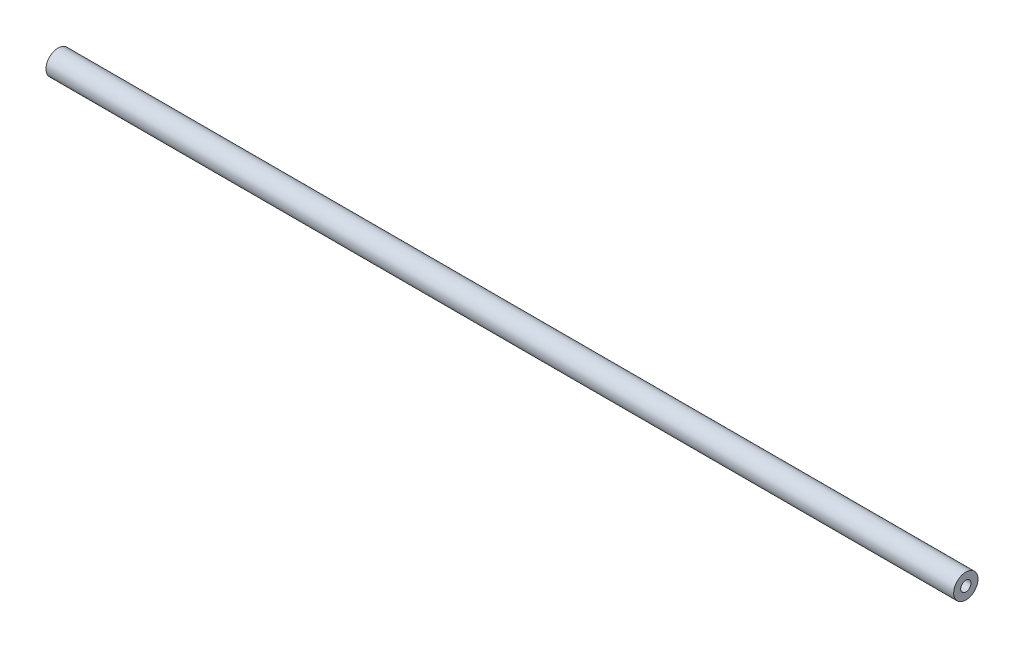
SolidWorks part; units mm, degrees
material "7075-T6 (SN)"
ref_plane "Front Plane" through (0, 0, 0) normal (0, 0, 1) x (1, 0, 0)
ref_plane "Top Plane" through (0, 0, 0) normal (0, 1, 0) x (1, 0, 0)
ref_plane "Right Plane" through (0, 0, 0) normal (1, 0, 0) x (0, 0, -1)
sketch "Sketch1" plane through (0, 0, 0) normal (1, 0, 0) x (0, 0, -1)
  circle A1 centre (0, 0) radius 4.7625
  dimension "D1" = 9.525
extrude "Boss-Extrude1" add sketch "Sketch1" along normal mid plane 355.6 contours A1 region at (0, 0, 0)
hole_wizard "#10-32 Tapped Hole1" positions "3DSketch1" profile "Sketch2" tap size "#10-32" standard "ANSI Inch"
sketch3d "3DSketch1"
  line L0 (177.8, 0, 0) -> (-177.8, 0, 0) construction
  point P0 (177.8, 0, 0)
  point P7 (-177.8, 0, 0)
sketch "Sketch2" plane through (177.8, 0, 0) normal (0, 1, 0) x (0, 0, -1)
  line L0 (0, 0) -> (0, 13.2428)
  line L1 (0, 13.2428) -> (2.0193, 12.0294)
  line L2 (2.0193, 12.0294) -> (2.0193, 0)
  line L5 (2.0193, 0) -> (0, 0)
  line L10 (0, 13.2428) -> (-2.0193, 12.0294) construction
  line L11 (0, -6.35) -> (0, 107.95) construction
  dimension "Tap Drill Dia." = 4.0386
  dimension "Tap Drill Depth" = 12.0294
  dimension "Drill Angle" = 118
cosmetic thread "Hole Thread1"
cosmetic thread "Hole Thread2"
